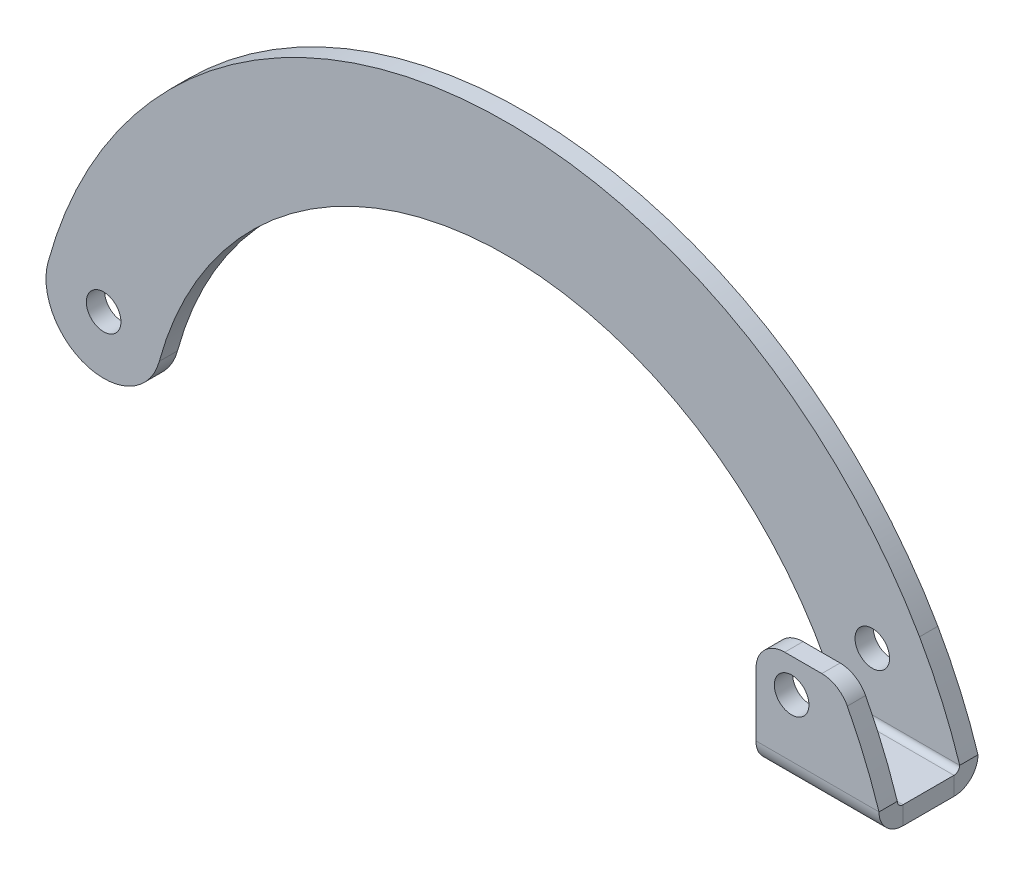
SolidWorks part; units mm, degrees
note: The reader was unsure of these and kept them because the rebuilt part matched: flange length of "Edge-Flange1", "Edge-Flange2".
ref_plane "Front Plane" through (0, 0, 0) normal (0, 0, 1) x (1, 0, 0)
ref_plane "Top Plane" through (0, 0, 0) normal (0, 1, 0) x (1, 0, 0)
ref_plane "Right Plane" through (0, 0, 0) normal (1, 0, 0) x (0, 0, -1)
sketch "Sketch1" plane through (0, 0, 0) normal (0, 0, 1) x (1, 0, 0)
  line L0 (0, 0) -> (0, 110) construction
  line L1 (0, 110) -> (141.3585, 3.4787) construction
  line L3 (10, 89.9431) -> (130.0262, -0.5031) construction
  line L4 (-10, 11.9941) -> (-10, 130.0569) construction
  line L5 (-10, 130.0569) -> (90.6434, 54.2167) construction
  line L9 (127.1789, -0.5031) -> (143.3721, -0.5031)
  line L12 (143.3721, -0.5031) -> (143.3721, 11.9941) construction
  line L13 (143.3721, -0.5031) -> (148.5349, -0.5031)
  line L14 (-10, 0) -> (-10, 130.0569) construction
  line L15 (-10, 130.0569) -> (147.3766, 11.4651) construction
  line L16 (10, 89.9431) -> (135.3403, -4.5076) construction
  line L17 (10, 0) -> (10, 89.9431) construction
  circle A0 centre (133.3721, 9.4969) radius 3 construction
  circle A1 centre (0, -6.6279) radius 3 construction
  circle A2 centre (69.9604, -25.6486) radius 72.5 construction
  arc A3 (143.3721, 11.9941) -> (-9.6497, -4.0043) centre (69.9604, -25.6486) ccw
  arc A4 (127.1789, -0.5031) -> (9.6497, -9.2514) centre (69.9604, -25.6486) ccw
  arc A5 (-9.6497, -4.0043) -> (9.6497, -9.2514) centre (0, -6.6279) ccw
  arc A6 (148.5349, -0.5031) -> (143.3721, 11.9941) centre (69.9604, -25.6486) ccw
  circle A7 centre (69.9604, -25.6486) radius 82.5 construction
  circle A8 centre (69.9604, -25.6486) radius 62.5 construction
  point P25 (129.0788, -18.697)
  point P26 (149.0788, -18.697)
  dimension "D8" = 6
  dimension "D12" = 145
  dimension "D1" = 110
  dimension "D2" = 177
  dimension "D3" = 53
  dimension "D7" = 10
  dimension "D9" = 10
  dimension "D10" = 10
  dimension "D4" = 10
  dimension "D5" = 10
  dimension "D13" = 10
  dimension "D14" = 10
base flange "Base-Flange1" sketch "Sketch1" thickness 3.175 reverse thickness direction no parameters "D1"=1
edge flange "Edge-Flange1" sketch "Sketch8" flange angle 90 flange length 14 flange position bend outside bend radius 1 thickness 3.175 parameters "D6"=10
sketch "Sketch8" plane through (0, -0.5031, 0) normal (0, 1, 0) x (-1, 0, 0)
  line L2 (-148.5349, 0) -> (-148.5349, 10.825)
  line L3 (-148.5349, 10.825) -> (-127.1789, 10.825)
  line L4 (-127.1789, 10.825) -> (-127.1789, 0)
  line L5 (-127.1789, 0) -> (-148.5349, 0) construction
  line L6 (-127.1789, 0) -> (-148.5349, 0)
bend "EdgeBend1" bend radius 1 bend angle 90 parameters "D5"=1
edge flange "Edge-Flange2" sketch "Sketch11" flange angle 90 flange length 20 flange position material outside bend radius 1 thickness 3.175 parameters "D6"=10
sketch "Sketch11" plane through (0, -1.5031, 10.825) normal (0, 0, 1) x (1, 0, 0)
  line L0 (127.1789, 0) -> (148.5349, 0) construction
  line L1 (127.1789, 0) -> (148.5349, 0)
  line L2 (148.5349, 0) -> (148.5349, 16.825)
  line L3 (148.5349, 16.825) -> (127.1789, 16.825)
  line L4 (127.1789, 16.825) -> (127.1789, 0)
bend "EdgeBend2" bend radius 1 bend angle 90 parameters "D5"=2
sketch "Sketch12" plane through (0, 0, 0) normal (0, 0, 1) x (1, 0, 0)
  line L3 (127.1789, 15.3219) -> (148.5349, 15.3219) construction
  line L4 (141.5682, 15.3219) -> (148.5349, 15.3219)
  line L5 (148.5349, 15.3219) -> (148.5349, -0.5031)
  circle A0 centre (133.3721, 9.4969) radius 3 construction
  circle A1 centre (0, -6.6279) radius 3 construction
  circle A2 centre (133.3721, 9.4969) radius 3
  circle A3 centre (0, -6.6279) radius 3
  arc A6 (148.5349, -0.5031) -> (143.3721, 11.9941) centre (69.9604, -25.6486) ccw construction
  arc A8 (143.3721, 11.9941) -> (-9.6497, -4.0043) centre (69.9604, -25.6486) ccw construction
  arc A9 (148.5349, -0.5031) -> (143.3721, 11.9941) centre (69.9604, -25.6486) ccw
  arc A10 (143.3721, 11.9941) -> (141.5682, 15.3219) centre (69.9604, -25.6486) ccw
extrude "Cut-Extrude1" cut sketch "Sketch12" against normal through all both and the other way through all
fillet "Fillet1" radius 5 2 edges at (127.1789, 15.3219, 12.4125) (141.5682, 15.3219, 12.4125)
sketch "Bend-Lines1" [suppressed] plane through (0, 0, 0) normal (0, 1, 0) x (1, 0, 0)
sketch "Bounding-Box1" [suppressed] plane through (0, 0, 0) normal (0, 1, 0) x (1, 0, 0)
sheet metal parameters "Sheet-Metal10" thickness 3.175 parameters "D1"=1
flat pattern "Flat-Pattern10" [suppressed]
sketch "Bend-Lines2" plane through (0, 0, 0) normal (0, 1, 0) x (1, 0, 0)
sketch3d "Bounding-Box2" [suppressed]
  line L0 (78.8184, 7.9965, 0) -> (-78.5745, 25.1455, 0) construction
  line L1 (85.9686, 73.6214, 0) -> (-71.4243, 90.7704, 0) construction
  line L2 (78.8184, 7.9965, 0) -> (85.9686, 73.6214, 0) construction
  line L3 (-78.5745, 25.1455, 0) -> (-71.4243, 90.7704, 0) construction
sheet metal parameters "Sheet-Metal11" thickness 3.175 parameters "D1"=1
flat pattern "Flat-Pattern10"
sketch "Bend-Lines2" plane through (0, 0, 0) normal (0, 0, 1) x (1, 0, 0)
  line L0 (127.1789, -1.5353) -> (148.3714, -1.5353) construction
  line L1 (127.1789, -1.5353) -> (148.3714, -1.5353) construction
sketch3d "Bounding-Box2" [suppressed]
  line L0 (-74.4702, 88.6632, 0) -> (84.6904, 76.0442, 0) construction
  line L1 (-80.7194, 9.8424, 0) -> (78.4411, -2.7766, 0) construction
  line L2 (-74.4702, 88.6632, 0) -> (-80.7194, 9.8424, 0) construction
  line L3 (84.6904, 76.0442, 0) -> (78.4411, -2.7766, 0) construction
bend of the flat pattern "Flatten-<EdgeBend1>1"
sheet metal parameters "Sheet-Metal12" thickness 3.175 parameters "D1"=1
flat pattern "Flat-Pattern10"
sketch "Bend-Lines2" plane through (0, 0, 0) normal (0, 0, 1) x (1, 0, 0)
  line L0 (127.1789, -1.5353) -> (148.3714, -1.5353) construction
  line L1 (127.1789, -1.5353) -> (148.3714, -1.5353) construction
  line L2 (127.1789, -27.7748) -> (148.5349, -27.7748) construction
  line L3 (127.1789, -27.7748) -> (148.5349, -27.7748) construction
sketch3d "Bounding-Box2" [suppressed]
  line L0 (-62.2115, 98.6464, 0) -> (97.2439, 62.5977, 0) construction
  line L1 (-81.9193, 11.472, 0) -> (77.5361, -24.5766, 0) construction
  line L2 (-62.2115, 98.6464, 0) -> (-81.9193, 11.472, 0) construction
  line L3 (97.2439, 62.5977, 0) -> (77.5361, -24.5766, 0) construction
bend of the flat pattern "Flatten-<EdgeBend1>1"
bend of the flat pattern "Flatten-<EdgeBend2>1"
sheet metal parameters "Sheet-Metal13" thickness 3.175 parameters "D1"=1
flat pattern "Flat-Pattern10"
sketch "Bend-Lines2" plane through (0, 0, 0) normal (0, 0, 1) x (1, 0, 0)
  line L0 (127.1789, -2.5353) -> (148.5349, -2.5353) construction
  line L1 (127.1789, -2.5353) -> (148.5349, -2.5353) construction
  line L2 (127.1789, -15.4248) -> (148.5349, -15.4248) construction
  line L3 (127.1789, -15.4248) -> (148.5349, -15.4248) construction
sketch3d "Bounding-Box2" [suppressed]
  line L0 (-70.8587, 92.056, 0) -> (86.6278, 72.2602, 0) construction
  line L1 (-81.1295, 10.346, 0) -> (76.357, -9.4498, 0) construction
  line L2 (-70.8587, 92.056, 0) -> (-81.1295, 10.346, 0) construction
  line L3 (86.6278, 72.2602, 0) -> (76.357, -9.4498, 0) construction
bend of the flat pattern "Flatten-<EdgeBend1>1"
bend of the flat pattern "Flatten-<EdgeBend2>1"
